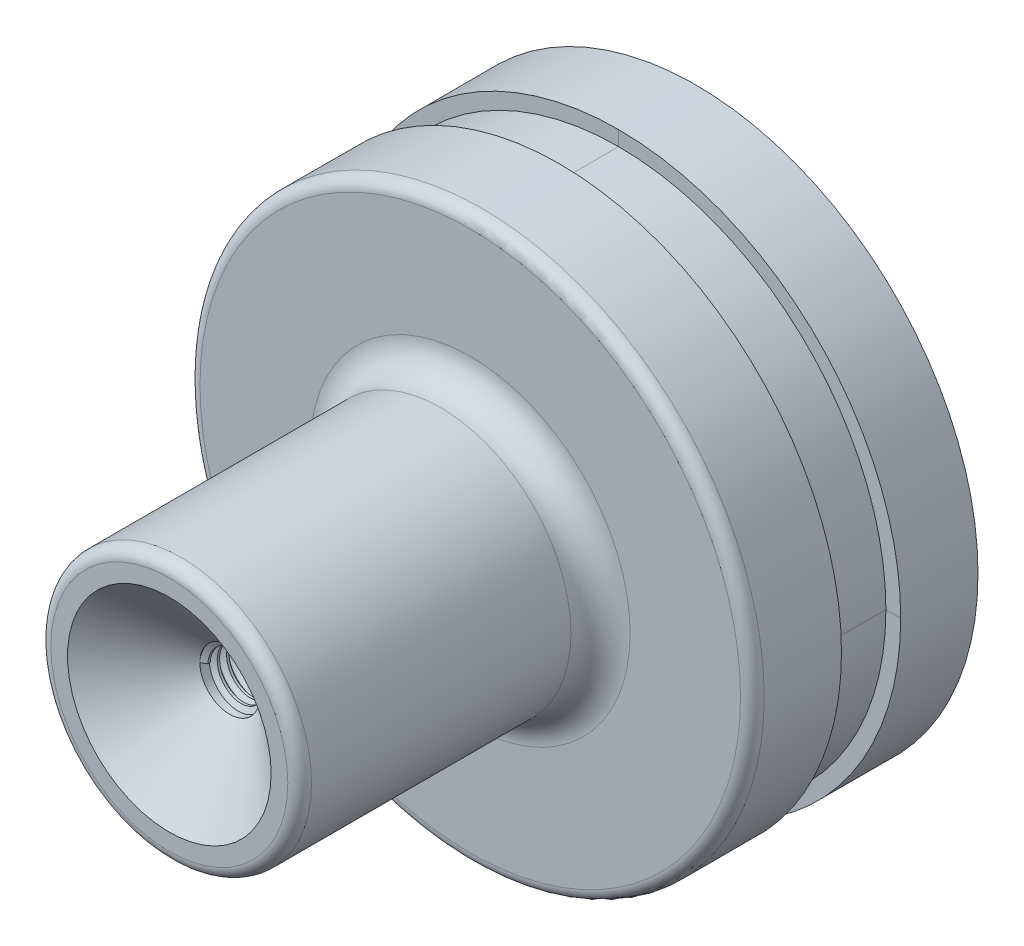
SolidWorks part; units mm, degrees
ref_plane "Front Plane" through (0, 0, 0) normal (0, 0, 1) x (1, 0, 0)
ref_plane "Top Plane" through (0, 0, 0) normal (0, 1, 0) x (1, 0, 0)
ref_plane "Right Plane" through (0, 0, 0) normal (1, 0, 0) x (0, 0, -1)
sketch "Sketch1" plane through (0, 0, 0) normal (0, 0, 1) x (1, 0, 0)
  circle A0 centre (0, 0) radius 47.625
extrude "Boss-Extrude1" add sketch "Sketch1" along normal blind 88.9
sketch "Sketch2" plane through (0, 0, 88.9) normal (0, 0, 1) x (1, 0, 0)
  circle A0 centre (0, 0) radius 22
extrude "Cut-Extrude2" cut sketch "Sketch2" against normal blind 50.8 flip side to cut
hole_wizard "CSK for 3/8 Flat Head Machine Screw (100)1" positions "Sketch4" profile "Sketch5" countersink size "3/8" standard "ANSI Inch"
sketch "Sketch4" plane through (0, 0, 88.9) normal (0, 0, 1) x (1, 0, 0)
  point P0 (0, 0)
sketch "Sketch5" plane through (0, 0, 88.9) normal (1, 0, 0) x (0, -1, 0)
  line L0 (0, 0) -> (0, 28.0295)
  line L1 (0, 28.0295) -> (5.0419, 25)
  line L2 (5.0419, 25) -> (5.0419, 10.1896)
  line L3 (5.0419, 10.1896) -> (17.1854, 0)
  line L5 (17.1854, 0) -> (0, 0)
  line L6 (-5.0419, 10.1896) -> (-17.1854, 0) construction
  line L10 (0, 28.0295) -> (-5.0419, 25) construction
  line L11 (0, -6.35) -> (0, 107.95) construction
  dimension "Hole Dia." = 10.0838
  dimension "Hole Depth" = 25
  dimension "Near C'Sink Dia." = 34.3708
  dimension "Near C'Sink Angle" = 100
  dimension "Drill Angle" = 118
thread "Thread1" pitch 1.5875 method extrude profile "Thread Profile1" start angle 0, offset 0, length 16, pitch 1.5875, diameter 10.0838
ref_plane "Plane1" through (-5.0419, 0, 78.7104) normal (0, -1, 0) x (-1, 0, 0)
sketch "Thread Profile1" plane through (-5.0419, 0, 78.7104) normal (0, -1, 0) x (-1, 0, 0)
  line L0 (0, 0) -> (0, 1.5875) construction
  line L11 (0, 0) -> (0, 1.3891)
  line L12 (0, 1.3891) -> (-0.8593, 0.893)
  line L13 (-0.8593, 0.893) -> (-0.8593, 0.4961)
  line L15 (-0.8593, 0.4961) -> (0, 0)
  line L17 (-0.8593, 0.6945) -> (0, 0.6945) construction
  point P2 (0, 0)
  dimension "Pitch" = 1.5875
  dimension "Profile_Angle" = 60
  dimension "Profile_Land" = 0.3969
  dimension "Profile_Height" = 0.8593
fillet "Fillet1" radius 2 2 edges at (22, 0, 88.9) (47.625, 0, 38.1)
fillet "Fillet2" radius 5 1 edges at (22, 0, 38.1)
sketch "Sketch15" plane through (0, 0, 0) normal (0, 0, -1) x (-1, 0, 0)
  circle A1 centre (0, 0) radius 40.8125
extrude "Cut-Extrude3" cut sketch "Sketch15" against normal blind 15
sketch "Sketch19" plane through (0, 0, 0) normal (1, 0, 0) x (0, 0, -1)
  line L3 (-13.05, 45.125) -> (-23.05, 45.125)
  line L4 (-13.05, 45.125) -> (-13.05, 50.125)
  line L5 (-13.05, 50.125) -> (-23.05, 50.125)
  line L6 (-23.05, 45.125) -> (-23.05, 50.125)
  line L7 (-13.05, 45.125) -> (-23.05, 50.125) construction
  line L8 (-13.05, 50.125) -> (-23.05, 45.125) construction
sweep "Cut-Sweep1" cut profiles "Sketch19" path edge at (47.625, 0, 36.1)
scale "Scale1" scale about centroid uniform scaling yes scale factor 0.49
scale "Scale2" scale about centroid uniform scaling yes scale factor 0.894
scale "Scale3" scale about centroid uniform scaling yes scale factor 0.8184
